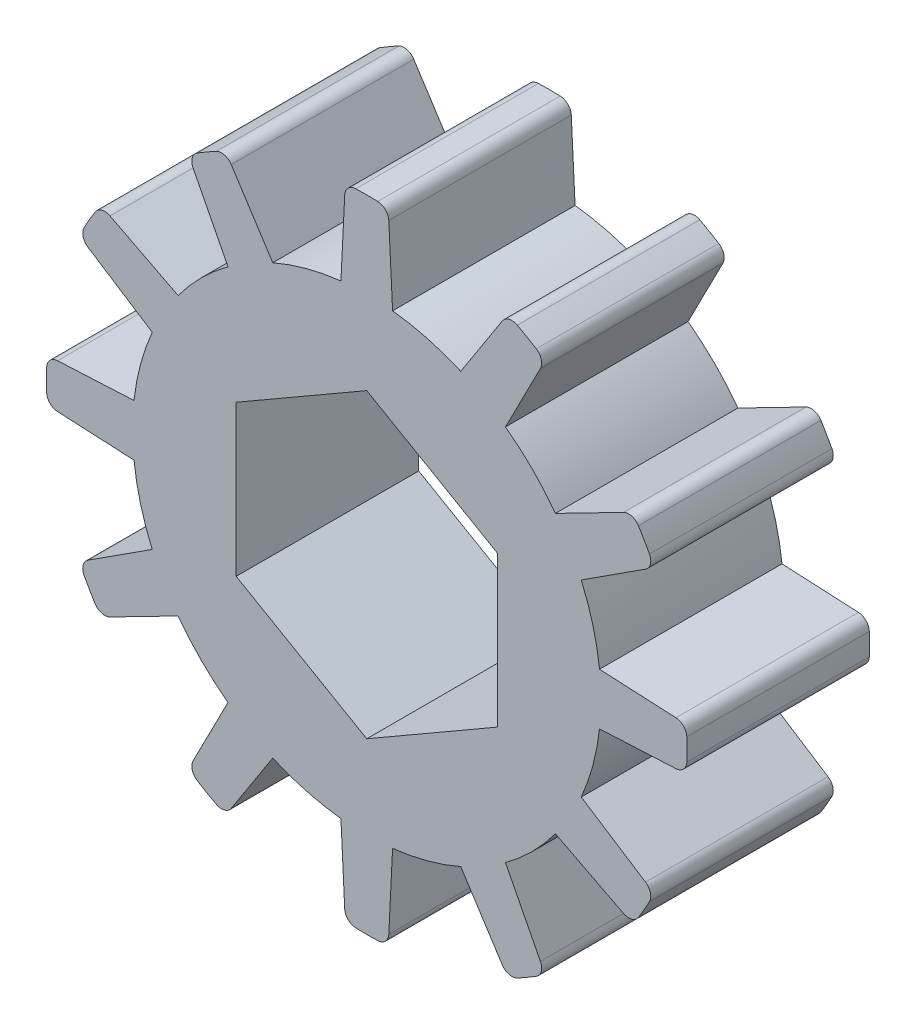
SolidWorks part; units mm, degrees
material "ABS"
ref_plane "Alzado" through (0, 0, 0) normal (0, 0, 1) x (1, 0, 0)
ref_plane "Planta" through (0, 0, 0) normal (0, 1, 0) x (1, 0, 0)
ref_plane "Vista lateral" through (0, 0, 0) normal (1, 0, 0) x (0, 0, -1)
sketch "Croquis1" plane through (0, 0, 0) normal (0, 0, 1) x (1, 0, 0)
  line L0 (0, 0) -> (0, 4.6049) construction
  line L1 (0.375, 5.5679) -> (0.45, 4.0556)
  line L2 (-0.375, 5.5679) -> (-0.45, 4.0556)
  line L3 (2.4592, 5.0094) -> (1.6381, 3.7373)
  line L4 (3.1087, 4.6344) -> (2.4175, 3.2873)
  line L5 (4.6344, 3.1087) -> (3.2873, 2.4175)
  line L6 (5.0094, 2.4592) -> (3.7373, 1.6381)
  line L7 (5.5679, 0.375) -> (4.0556, 0.45)
  line L8 (5.5679, -0.375) -> (4.0556, -0.45)
  line L9 (5.0094, -2.4592) -> (3.7373, -1.6381)
  line L10 (4.6344, -3.1087) -> (3.2873, -2.4175)
  line L11 (3.1087, -4.6344) -> (2.4175, -3.2873)
  line L12 (2.4592, -5.0094) -> (1.6381, -3.7373)
  line L13 (0.375, -5.5679) -> (0.45, -4.0556)
  line L14 (-0.375, -5.5679) -> (-0.45, -4.0556)
  line L15 (-2.4592, -5.0094) -> (-1.6381, -3.7373)
  line L16 (-3.1087, -4.6344) -> (-2.4175, -3.2873)
  line L17 (-4.6344, -3.1087) -> (-3.2873, -2.4175)
  line L18 (-5.0094, -2.4592) -> (-3.7373, -1.6381)
  line L19 (-5.5679, -0.375) -> (-4.0556, -0.45)
  line L20 (-5.5679, 0.375) -> (-4.0556, 0.45)
  line L21 (-5.0094, 2.4592) -> (-3.7373, 1.6381)
  line L22 (-4.6344, 3.1087) -> (-3.2873, 2.4175)
  line L23 (-3.1087, 4.6344) -> (-2.4175, 3.2873)
  line L24 (-2.4592, 5.0094) -> (-1.6381, 3.7373)
  circle A0 centre (0, 0) radius 0.5
  arc A1 (1.6381, 3.7373) -> (0.45, 4.0556) centre (0, 0) ccw
  arc A2 (3.1087, 4.6344) -> (2.4592, 5.0094) centre (0, 0) ccw
  arc A3 (5.0094, 2.4592) -> (4.6344, 3.1087) centre (0, 0) ccw
  arc A4 (5.5679, -0.375) -> (5.5679, 0.375) centre (0, 0) ccw
  arc A5 (4.6344, -3.1087) -> (5.0094, -2.4592) centre (0, 0) ccw
  arc A6 (2.4592, -5.0094) -> (3.1087, -4.6344) centre (0, 0) ccw
  arc A7 (-0.375, -5.5679) -> (0.375, -5.5679) centre (0, 0) ccw
  arc A8 (-3.1087, -4.6344) -> (-2.4592, -5.0094) centre (0, 0) ccw
  arc A9 (-5.0094, -2.4592) -> (-4.6344, -3.1087) centre (0, 0) ccw
  arc A10 (-5.5679, 0.375) -> (-5.5679, -0.375) centre (0, 0) ccw
  arc A11 (-4.6344, 3.1087) -> (-5.0094, 2.4592) centre (0, 0) ccw
  arc A12 (-2.4592, 5.0094) -> (-3.1087, 4.6344) centre (0, 0) ccw
  arc A13 (0.375, 5.5679) -> (-0.375, 5.5679) centre (0, 0) ccw
  arc A14 (3.2873, 2.4175) -> (2.4175, 3.2873) centre (0, 0) ccw
  arc A15 (4.0556, 0.45) -> (3.7373, 1.6381) centre (0, 0) ccw
  arc A16 (3.7373, -1.6381) -> (4.0556, -0.45) centre (0, 0) ccw
  arc A17 (2.4175, -3.2873) -> (3.2873, -2.4175) centre (0, 0) ccw
  arc A18 (0.45, -4.0556) -> (1.6381, -3.7373) centre (0, 0) ccw
  arc A19 (-1.6381, -3.7373) -> (-0.45, -4.0556) centre (0, 0) ccw
  arc A20 (-3.2873, -2.4175) -> (-2.4175, -3.2873) centre (0, 0) ccw
  arc A21 (-4.0556, -0.45) -> (-3.7373, -1.6381) centre (0, 0) ccw
  arc A22 (-3.7373, 1.6381) -> (-4.0556, 0.45) centre (0, 0) ccw
  arc A23 (-2.4175, 3.2873) -> (-3.2873, 2.4175) centre (0, 0) ccw
  arc A24 (-0.45, 4.0556) -> (-1.6381, 3.7373) centre (0, 0) ccw
  dimension "D1" = 0.9
  dimension "D2" = 1
  dimension "D4" = 1.5
  dimension "D3" = 0.75
  dimension "D6" = 1.23
  dimension "D5" = 12
extrude "Saliente-Extruir1" add sketch "Croquis1" along normal blind 3.18
sketch "Croquis10" plane through (0, 0, 0) normal (0, 0, -1) x (-1, 0, 0)
  line L1 (0, -2.6269) -> (2.275, -1.3135)
  line L2 (2.275, -1.3135) -> (2.275, 1.3135)
  line L3 (2.275, 1.3135) -> (0, 2.6269)
  line L4 (0, 2.6269) -> (-2.275, 1.3135)
  line L5 (-2.275, 1.3135) -> (-2.275, -1.3135)
  line L6 (-2.275, -1.3135) -> (0, -2.6269)
  circle A0 centre (0, 0) radius 2.275 construction
  dimension "D1" = 4.55
extrude "Cortar-Extruir3" cut sketch "Croquis10" against normal through all
fillet "Redondeo1" radius 0.2 24 edges at (5.5679, -0.375, 1.59) (-2.4592, -5.0094, 1.59) (-3.1087, -4.6344, 1.59) (0.375, -5.5679, 1.59) (-0.375, -5.5679, 1.59) (3.1087, -4.6344, 1.59) (2.4592, -5.0094, 1.59) (5.0094, -2.4592, 1.59) (4.6344, -3.1087, 1.59) (-4.6344, -3.1087, 1.59) (-5.0094, -2.4592, 1.59) (-5.5679, -0.375, 1.59) (-5.5679, 0.375, 1.59) (-5.0094, 2.4592, 1.59) (-4.6344, 3.1087, 1.59) (-3.1087, 4.6344, 1.59) (-2.4592, 5.0094, 1.59) (5.5679, 0.375, 1.59) (5.0094, 2.4592, 1.59) (4.6344, 3.1087, 1.59) (3.1087, 4.6344, 1.59) (2.4592, 5.0094, 1.59) (0.375, 5.5679, 1.59) (-0.375, 5.5679, 1.59)
